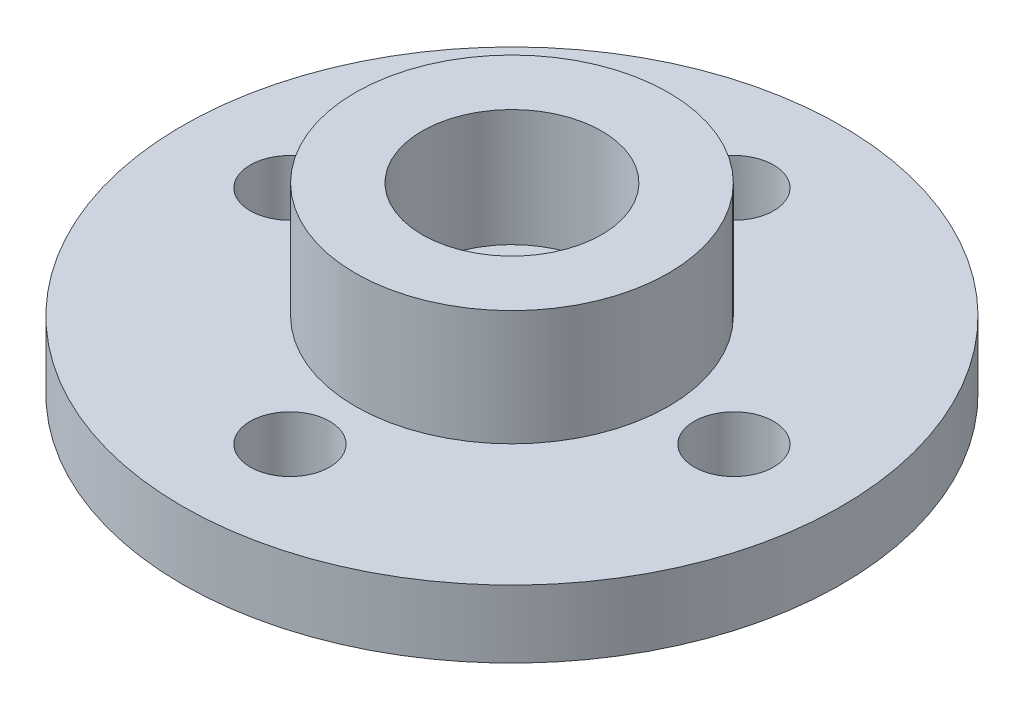
SolidWorks part; units mm, degrees
ref_plane "Front Plane" through (0, 0, 0) normal (0, 0, 1) x (1, 0, 0)
ref_plane "Top Plane" through (0, 0, 0) normal (0, 1, 0) x (1, 0, 0)
ref_plane "Right Plane" through (0, 0, 0) normal (1, 0, 0) x (0, 0, -1)
sketch "Sketch1" plane through (0, 0, 0) normal (0, 1, 0) x (1, 0, 0)
  circle A0 centre (0, 0) radius 10
  dimension "D1" = 20
extrude "Boss-Extrude1" add sketch "Sketch1" along normal blind 2.05
sketch "Sketch2" plane through (0, 2.05, 0) normal (0, 1, 0) x (1, 0, 0)
  circle A0 centre (0, 0) radius 4.75
  dimension "D1" = 9.5
extrude "Boss-Extrude2" add sketch "Sketch2" along normal blind 3.5
sketch "Sketch3" plane through (0, 5.55, 0) normal (0, 1, 0) x (1, 0, 0)
  circle A0 centre (0, 0) radius 2.725
  dimension "D1" = 5.45
extrude "Cut-Extrude1" cut sketch "Sketch3" against normal blind 3.55
sketch "Sketch4" plane through (0, 2, 0) normal (0, 1, 0) x (1, 0, 0)
  circle A0 centre (0, 0) radius 1.375
  dimension "D1" = 2.75
extrude "Cut-Extrude2" cut sketch "Sketch4" against normal blind 3.55
sketch "Sketch5" plane through (0, 0, 0) normal (0, -1, 0) x (1, 0, 0)
  circle A0 centre (-6.735, 0) radius 1.205
  dimension "D2" = 2.41
  dimension "D1" = 6.735
extrude "Cut-Extrude3" cut sketch "Sketch5" against normal blind 3.55
pattern_circular "CirPattern1" count 4 over 360 about axis through (0, -1.55, 0) along (0, 1, 0) of "Cut-Extrude3"
